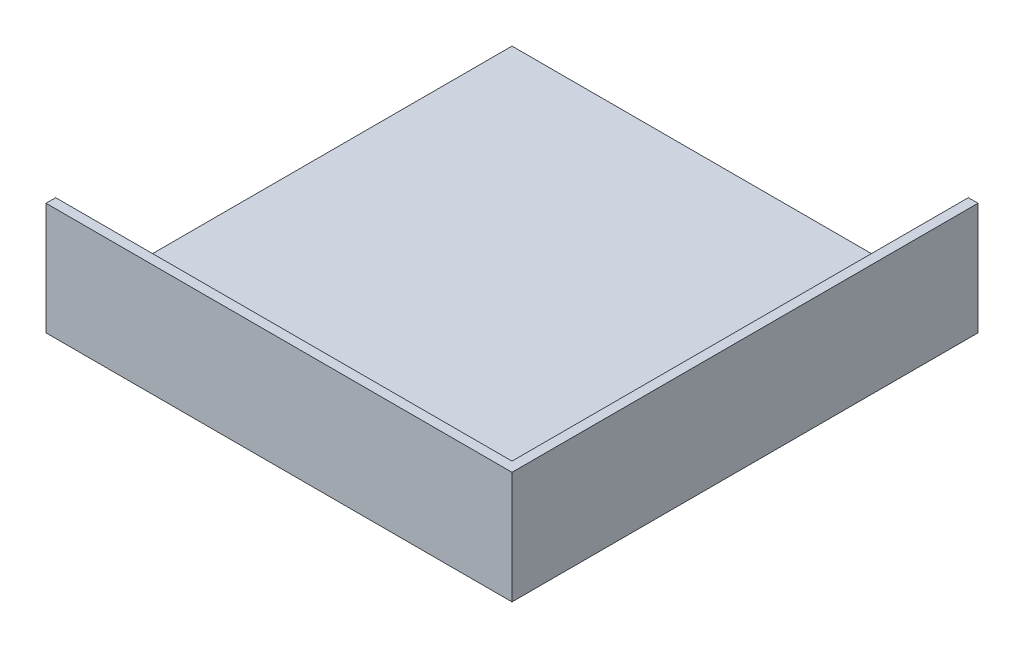
SolidWorks part; units mm, degrees
ref_plane "Front Plane" through (0, 0, 0) normal (0, 0, 1) x (1, 0, 0)
ref_plane "Top Plane" through (0, 0, 0) normal (0, 1, 0) x (1, 0, 0)
ref_plane "Right Plane" through (0, 0, 0) normal (1, 0, 0) x (0, 0, -1)
sketch "Sketch1" plane through (0, 0, 0) normal (0, 1, 0) x (1, 0, 0)
  line L1 (-96.2, 96.2) -> (96.2, 96.2)
  line L2 (-96.2, 96.2) -> (-96.2, -96.2)
  line L3 (-96.2, -96.2) -> (96.2, -96.2)
  line L4 (96.2, 96.2) -> (96.2, -96.2)
  line L5 (-96.2, 96.2) -> (96.2, -96.2) construction
  line L6 (-96.2, -96.2) -> (96.2, 96.2) construction
  point P0 (0, 0)
  dimension "D1" = 192.4
  dimension "D2" = 192.4
extrude "Boss-Extrude1" add sketch "Sketch1" along normal blind 6.35
sketch "Sketch2" plane through (0, 6.35, 0) normal (0, 1, 0) x (1, 0, 0)
  line L2 (-92.2, 92.2) -> (-92.2, -92.2)
  line L3 (-92.2, -92.2) -> (92.2, -92.2)
  line L4 (96.2, -96.2) -> (96.2, 96.2)
  line L5 (96.2, 96.2) -> (-96.2, 96.2)
  line L6 (-96.2, 96.2) -> (-96.2, -96.2)
  line L7 (-96.2, -96.2) -> (96.2, -96.2)
  line L10 (-96.2, 96.2) -> (-96.2, -96.2)
  line L11 (-96.2, -96.2) -> (96.2, -96.2)
  line L12 (92.2, 92.2) -> (-92.2, 92.2) construction
  line L13 (96.2, 96.2) -> (-96.2, 96.2) construction
  line L14 (92.2, -92.2) -> (92.2, 92.2) construction
  line L15 (96.2, -96.2) -> (96.2, 96.2) construction
  line L16 (-92.2, 92.2) -> (-92.2, 96.2)
  line L17 (96.2, 96.2) -> (-96.2, 96.2) construction
  line L18 (-92.2, 96.2) -> (-96.2, 96.2)
  line L19 (92.2, -92.2) -> (96.2, -92.2)
  line L20 (96.2, -96.2) -> (96.2, 96.2) construction
  line L21 (96.2, -92.2) -> (96.2, -96.2)
  dimension "D1" = 0
  dimension "D2" = 4
extrude "Boss-Extrude2" add sketch "Sketch2" along normal blind 40
sketch "Sketch3" plane through (0, 6.35, 0) normal (0, 1, 0) x (1, 0, 0)
  line L0 (-96.2, -96.2) -> (96.2, -96.2) construction
  line L1 (-96.2, 96.2) -> (-56.2, 96.2) construction
  line L2 (-96.2, 96.2) -> (-96.2, -96.2) construction
  line L3 (-96.2, -96.2) -> (-56.2, -96.2) construction
  line L4 (-56.2, 96.2) -> (-56.2, -96.2) construction
  line L5 (96.2, -92.2) -> (96.2, 96.2) construction
  line L6 (-96.2, 96.2) -> (96.2, 96.2) construction
  line L7 (-96.2, 96.2) -> (-96.2, 55.6473) construction
  line L8 (-96.2, 55.6473) -> (96.2, 55.6473) construction
  line L9 (96.2, 96.2) -> (96.2, 55.6473) construction
  line L10 (96.2, -76.2) -> (-96.2, -76.2) construction
  line L11 (-96.2, -96.2) -> (96.2, -96.2) construction
  line L12 (-96.2, -96.2) -> (-96.2, -56.2) construction
  line L13 (-96.2, -56.2) -> (96.2, -56.2) construction
  line L14 (96.2, -96.2) -> (96.2, -56.2) construction
  line L15 (-76.2, -96.2) -> (-76.2, 96.2) construction
  line L16 (96.2, 75.9237) -> (-96.2, 75.9237) construction
  circle A0 centre (-76.2, -76.2) radius 2.25
  circle A1 centre (-76.2, 75.9237) radius 2.25
  circle A2 centre (96.2, -76.2) radius 2.25
  point P15 (96.2, -76.2)
  point P21 (-76.2, -76.2)
  point P23 (-76.2, 75.9237)
  point P33 (96.2, -76.2)
  dimension "D4" = 4.5
  dimension "D1" = 40
  dimension "D2" = 40.5527
  dimension "D3" = 40
hole_wizard "CBORE for M4 SHCS1" positions "Sketch3" profile "Sketch4" counterbore size "M4" standard "ANSI Metric" end condition up to next
sketch "Sketch4" plane through (96.2, 6.35, 76.2) normal (1, 0, 0) x (0, 0, 1)
  line L0 (0, 0) -> (0, 6.35)
  line L1 (0, 6.35) -> (2.25, 6.35)
  line L3 (2.25, 6.35) -> (2.25, 4)
  line L4 (2.25, 4) -> (4, 4)
  line L5 (4, 4) -> (4, 0)
  line L7 (4, 0) -> (0, 0)
  line L11 (0, -6.35) -> (0, 107.95) construction
  dimension "Thru Hole Dia." = 4.5
  dimension "Thru Hole Depth" = 6.35
  dimension "C'Bore Dia." = 8
  dimension "C'Bore Depth" = 4
mirror "Mirror1" about plane through (96.2, 6.35, -96.2) normal (-1, 0, 0) of bodies 103
delete or keep bodies "Body-Delete/Keep 1" type delete bodies bodies 103
equation "\"D2@Sketch1\"=384.8/2"
